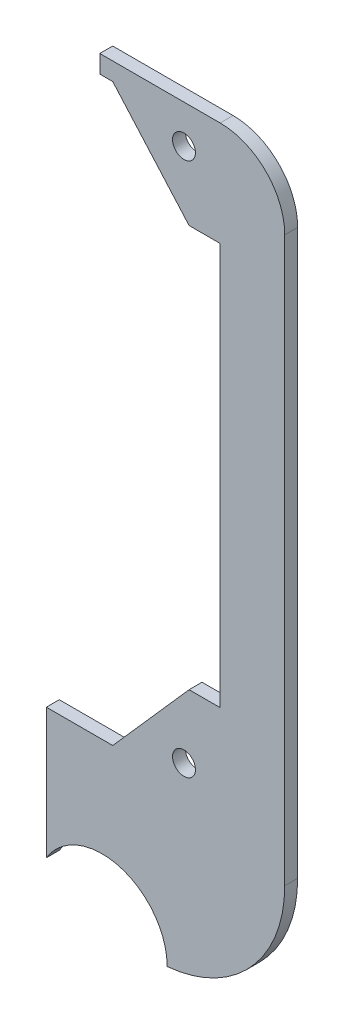
SolidWorks part; units mm, degrees
material "AISI 4130 Steel, normalized at 870C"
ref_plane "Front Plane" through (0, 0, 0) normal (0, 0, 1) x (1, 0, 0)
ref_plane "Top Plane" through (0, 0, 0) normal (0, 1, 0) x (1, 0, 0)
ref_plane "Right Plane" through (0, 0, 0) normal (1, 0, 0) x (0, 0, -1)
sketch "Sketch1" plane through (0, 0, 0) normal (0, 0, 1) x (1, 0, 0)
  line L0 (-15.5514, -28.9024) -> (0, -28.9024)
  line L8 (0, 119.888) -> (-28.8013, 119.888)
  line L15 (-5.1475, 99.3749) -> (-5.1475, 20.3749)
  line L17 (-11.5, 59.9251) -> (0, 59.944) construction
  line L22 (-5.1475, 20.3749) -> (-11.2475, 20.3749)
  line L23 (-11.2475, 20.3749) -> (-26.2475, 3.3749)
  line L24 (-26.2475, 3.3749) -> (-39.3002, 3.3749)
  line L25 (-39.3002, 3.3749) -> (-39.3002, -22.2657)
  line L26 (-5.1475, 99.3749) -> (-11.2475, 99.3749)
  line L27 (-11.2475, 99.3749) -> (-26.2475, 116.3749)
  line L28 (-26.2475, 116.3749) -> (-28.8013, 116.3749)
  line L29 (-28.8013, 119.888) -> (-28.8013, 116.3749)
  line L30 (0, 119.888) -> (7.5525, 119.888)
  line L31 (7.5525, 119.888) -> (7.5525, -28.9024)
  line L32 (7.5525, -28.9024) -> (0, -28.9024)
  circle A0 centre (-12.2475, 112.3749) radius 2.25
  arc A2 (-15.5514, -28.9024) -> (-39.3002, -22.2657) centre (-28.3531, -28.9024) ccw
  arc A3 (-10.5975, 7.3749) -> (-13.8975, 7.3749) centre (-12.2475, 7.3749) ccw construction
  arc A4 (-10.5975, 7.3749) -> (-13.8975, 7.3749) centre (-12.2475, 7.3749) ccw construction
  arc A5 (-13.8975, 7.3749) -> (-10.5975, 7.3749) centre (-12.2475, 7.3749) ccw construction
  arc A6 (-13.8975, 7.3749) -> (-10.5975, 7.3749) centre (-12.2475, 7.3749) ccw construction
  circle A8 centre (-12.2475, 7.3749) radius 2.25
  dimension "D2" = 4.5
  dimension "D1" = 4.5
  dimension "D3" = 28.8013
  dimension "D4" = 52.451
extrude "Boss-Extrude1" add sketch "Sketch1" along normal blind 2.54
fillet "Fillet2" radius 12.7 1 edges at (7.5525, 119.888, 1.27)
fillet "Fillet1" radius 25.4 1 edges at (7.5525, -28.9024, 1.27)
